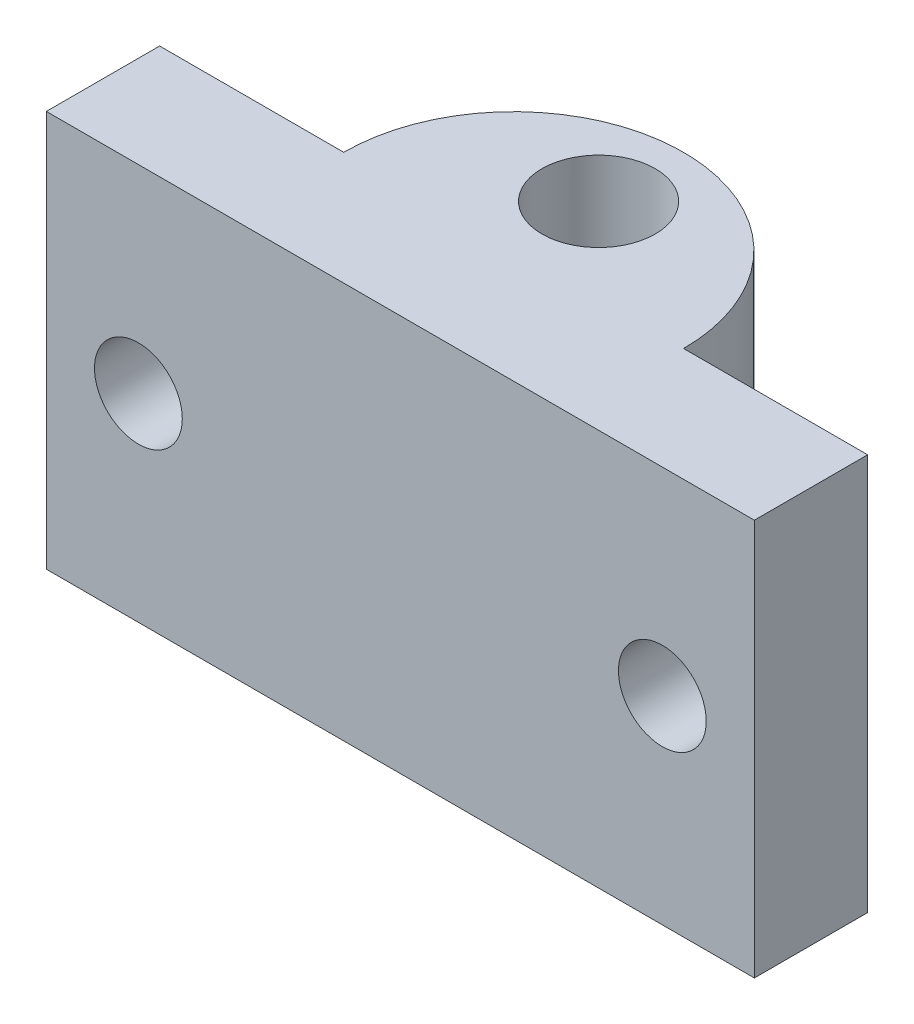
SolidWorks part; units mm, degrees
ref_plane "前视基准面" through (0, 0, 0) normal (0, 0, 1) x (1, 0, 0)
ref_plane "上视基准面" through (0, 0, 0) normal (0, 1, 0) x (1, 0, 0)
ref_plane "右视基准面" through (0, 0, 0) normal (1, 0, 0) x (0, 0, -1)
other "Configuration Table"
sketch "草图1" plane through (0, 0, 0) normal (0, 0, 1) x (1, 0, 0)
  line L0 (0, 0) -> (50, 0)
  line L1 (50, 0) -> (50, -28)
  line L2 (50, -28) -> (0, -28)
  line L3 (0, -28) -> (0, 0)
  line L4 (0, -14) -> (6.5, -14)
  line L5 (6.5, -14) -> (43.5, -14)
  circle A0 centre (6.5, -14) radius 3.1
  circle A1 centre (43.5, -14) radius 3.1
  dimension "D1" = 50
  dimension "D2" = 28
  dimension "D3" = 6.5
  dimension "D4" = 37
extrude "凸台-拉伸1" add sketch "草图1" along normal blind 8 contours A1 A0 L3 L2 L1 L0 | L5 A0 L4 | L4 A0 L5 | A1 region at (43.5, -10.9877, 0) region at (6.5, -12.6843, 0) region at (6.5, -15.3157, 0) region at (25, -0.5731, 0)
sketch "草图2" plane through (0, -28, 0) normal (0, -1, 0) x (1, 0, 0)
  line L0 (25, 0) -> (13, 0)
  line L1 (50, 0) -> (0, 0) construction
  line L2 (25, 0) -> (37, 0)
  arc A0 (13, 0) -> (37, 0) centre (25, 0) ccw
  line M2 (0, 0) -> (50, 0)
  dimension "D1" = 13
extrude "凸台-拉伸2" add sketch "草图2" against normal up to surface (28 mm away) contours A0 M2 region at (25, -28, -5.093) up to face at (25, 0, 4)
sketch "草图3" plane through (0, -28, 0) normal (0, -1, 0) x (1, 0, 0)
  line L0 (25, -12) -> (25, 0)
  arc A0 (13, 0) -> (37, 0) centre (25, 0) ccw construction
  circle A1 centre (25, -6) radius 4
extrude "切除-拉伸1" cut sketch "草图3" along direction (0, 1, 0) on the side against the normal up to surface (28 mm away) contours L0 A1 | L0 A1 region at (23.3023, -28, -6) region at (26.6977, -28, -6) up to face at (25, 0, 0.6667)
extrude "切除-拉伸2" cut sketch "草图1<4>" along normal up to surface (8 mm away) contours L5 A0 L4 | L4 A0 L5 | A1 region at (43.5, -10.9877, 0) region at (6.5, -12.6843, 0) region at (6.5, -15.3157, 0) up to face at (25, -14, 8)
sketch "草图1<4>" plane through (0, 0, 0) normal (0, 0, 1) x (1, 0, 0) same geometry as "草图1"
